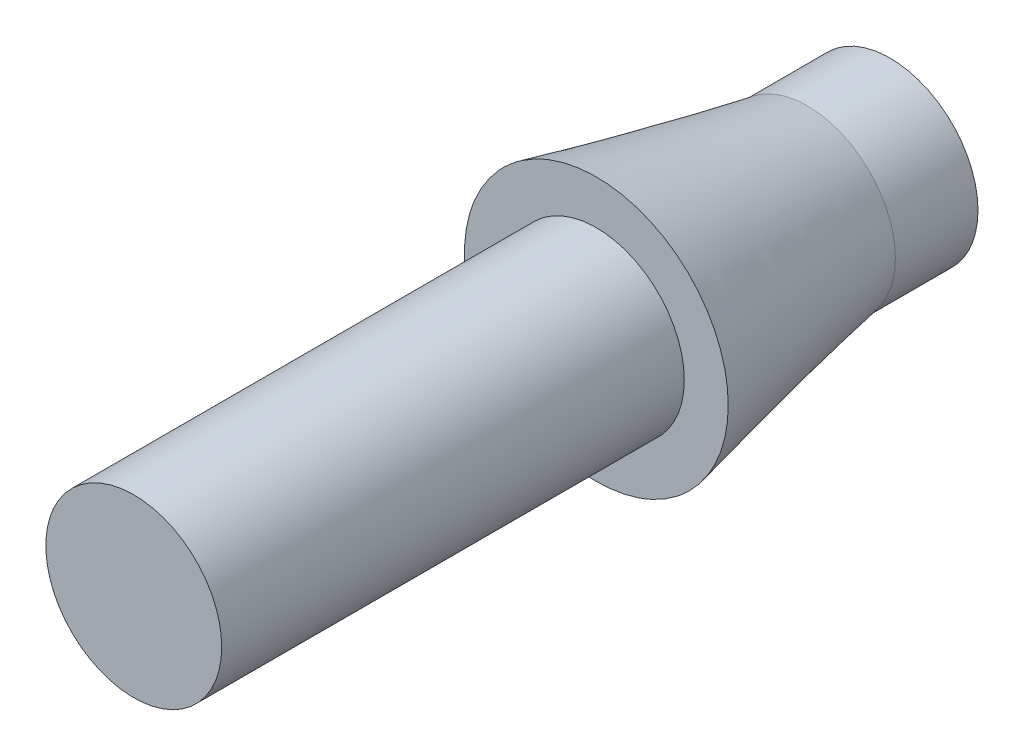
SolidWorks part; units mm, degrees
ref_plane "Front Plane" through (0, 0, 0) normal (0, 0, 1) x (1, 0, 0)
ref_plane "Top Plane" through (0, 0, 0) normal (0, 1, 0) x (1, 0, 0)
ref_plane "Right Plane" through (0, 0, 0) normal (1, 0, 0) x (0, 0, -1)
sketch "Sketch1" plane through (0, 0, 0) normal (0, 0, 1) x (1, 0, 0)
  circle A0 centre (0, 0) radius 5
extrude "Boss-Extrude1" add sketch "Sketch1" along normal blind 43
ref_plane "Plane1" through (0, 0, 4.7) normal (0, 0, 1) x (1, 0, 0)
sketch "Sketch2" plane through (0, 0, 4.7) normal (0, 0, 1) x (1, 0, 0)
  circle A0 centre (0, 0) radius 5
ref_plane "Plane2" through (0, 0, 16.7) normal (0, 0, 1) x (1, 0, 0)
sketch "Sketch3" plane through (0, 0, 16.7) normal (0, 0, 1) x (1, 0, 0)
  circle A0 centre (0, 0) radius 7.5
  dimension "D1" = 15
loft "Loft1" add profiles "Sketch3", "Sketch2" connector at (3.9228, -6.3923, 16.7) connector at (3.8304, -3.2137, 4.7)
